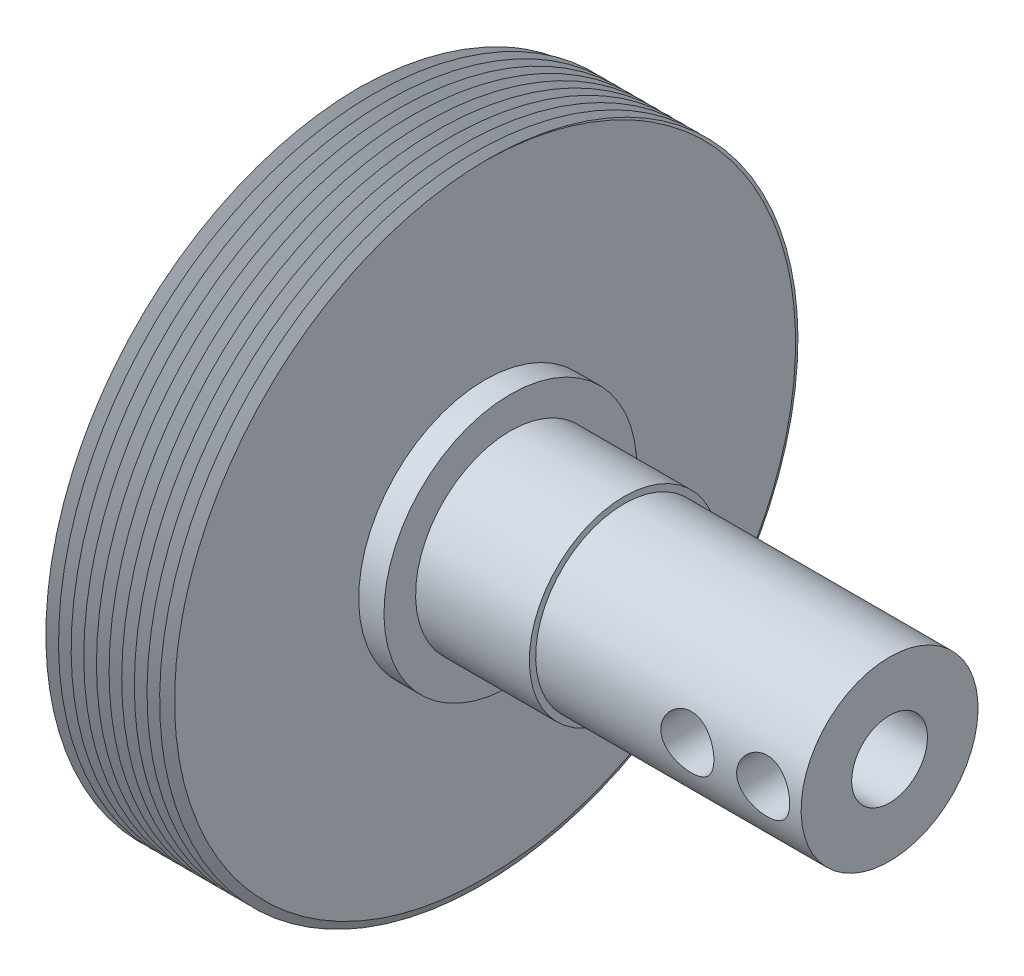
SolidWorks part; units mm, degrees
ref_plane "Front Plane" through (0, 0, 0) normal (0, 0, 1) x (1, 0, 0)
ref_plane "Top Plane" through (0, 0, 0) normal (0, 1, 0) x (1, 0, 0)
ref_plane "Right Plane" through (0, 0, 0) normal (1, 0, 0) x (0, 0, -1)
sketch "Sketch1" plane through (0, 0, 0) normal (0, 0, 1) x (1, 0, 0)
  line L4 (-12.8957, 0) -> (28.1974, 0) construction
  line L5 (0, 0) -> (0, 25)
  line L6 (0, 25) -> (10, 25)
  line L7 (10, 25) -> (10, 10)
  line L8 (10, 10) -> (12, 10)
  line L9 (12, 10) -> (12, 7.5)
  line L10 (12, 7.5) -> (21, 7.5)
  line L13 (42, 7) -> (42, 3)
  line L14 (28.1974, 0) -> (0, 0)
  line L15 (42, 3) -> (30, 3)
  line L16 (30, 3) -> (28.1974, 0)
  line L17 (67.8432, 0) -> (1087.5353, 0) construction
  line L18 (12, 10) -> (11, 10) construction
  line L19 (11, 10) -> (11, 17.5) construction
  line L20 (11, 17.5) -> (10, 17.5) construction
  line L21 (11, 17.5) -> (13, 17.5) construction
  line L22 (13, 17.5) -> (13, 10) construction
  line L23 (13, 10) -> (11, 10) construction
  line L24 (13, 17.5) -> (14, 17.5) construction
  line L25 (14, 17.5) -> (14, 10) construction
  line L26 (14, 10) -> (13, 10) construction
  line L27 (19, 17.5) -> (19, 10) construction
  line L28 (19, 10) -> (20, 10) construction
  line L29 (20, 10) -> (20, 17.5) construction
  line L30 (20, 17.5) -> (19, 17.5) construction
  line L31 (20, 17.5) -> (22, 17.5) construction
  line L32 (22, 17.5) -> (22, 10) construction
  line L33 (22, 10) -> (20, 10) construction
  line L34 (22, 17.5) -> (23, 17.5) construction
  line L35 (23, 17.5) -> (23, 10) construction
  line L36 (23, 10) -> (22, 10) construction
  line L37 (14, 10.5) -> (19, 10.5) construction
  line L38 (14, 7.5) -> (14, 8.5) construction
  line L39 (14, 8.5) -> (19, 8.5) construction
  line L40 (19, 8.5) -> (19, 7.5) construction
  line L41 (14, 9.5) -> (19, 9.5) construction
  line L42 (16.5, 10.5) -> (16.5, 9.5) construction
  line L43 (21, 7.5) -> (21, 7)
  line L44 (21, 7) -> (42, 7)
  line L45 (23, 17.5) -> (29, 17.5) construction
  line L46 (29, 17.5) -> (29, 7) construction
  circle A0 centre (33, 0) radius 2 construction
  circle A1 centre (39, 0) radius 2 construction
  dimension "D21" = 4
  dimension "D1" = 25
  dimension "D2" = 10
  dimension "D3" = 6
  dimension "D4" = 1
  dimension "D5" = 1
  dimension "D6" = 2
  dimension "D7" = 15
  dimension "D8" = 20
  dimension "D9" = 2
  dimension "D10" = 17.5
  dimension "D11" = 10.5
  dimension "D12" = 1
  dimension "D13" = 5
  dimension "D14" = 14
  dimension "D15" = 2
  dimension "D16" = 6
  dimension "D17" = 12
  dimension "D18" = 59
  dimension "D19" = 3
  dimension "D20" = 6
revolve "Revolve1" add sketch "Sketch1" angle 360 about L14
sketch "Sketch2" plane through (0, 0, 0) normal (0, 0, 1) x (1, 0, 0)
  line L0 (0, 25) -> (-0.5, 24.134)
  line L1 (-0.5, 24.134) -> (-1, 25)
  line L2 (-1, 25) -> (-1, 26)
  line L3 (-1, 26) -> (0, 26)
  line L4 (0, 26) -> (0, 25)
  point P3 (-0.5, 24.508)
  dimension "D1" = 1
  dimension "D2" = 60
  dimension "D3" = 1
sketch "Sketch3" plane through (0, 0, 0) normal (-1, 0, 0) x (0, 0, 1)
  circle A0 centre (0, 0) radius 25 construction
  circle A1 centre (0, 0) radius 25
curve "Helix/Spiral1" pitch 1 height 50 turns 50
sweep "Cut-Sweep1" cut profiles "Sketch2" path "Helix/Spiral1"
ref_plane "Plane1" through (0, 0, 7) normal (0, 0, 1) x (1, 0, 0)
hole_wizard "M5x0.8 Tapped Hole1" positions "Sketch4" profile "Sketch6" tap size "M5x0.8" standard "ANSI Metric"
sketch "Sketch4" plane through (0, 0, 7) normal (0, 0, 1) x (1, 0, 0)
  point P0 (39, 0)
  point P3 (33, 0)
sketch "Sketch6" plane through (39, 0, 7) normal (1, 0, 0) x (0, -1, 0)
  line L0 (0, 0) -> (0, 8.2618)
  line L1 (0, 8.2618) -> (2.1, 7)
  line L2 (2.1, 7) -> (2.1, 0)
  line L5 (2.1, 0) -> (0, 0)
  line L10 (0, 8.2618) -> (-2.1, 7) construction
  line L11 (0, -6.35) -> (0, 107.95) construction
  dimension "Tap Drill Dia." = 4.2
  dimension "Tap Drill Depth" = 7
  dimension "Drill Angle" = 118
cosmetic thread "Hole Thread1" parameters "D1"=6, "D2"=5
cosmetic thread "Hole Thread2" parameters "D1"=6, "D2"=5
